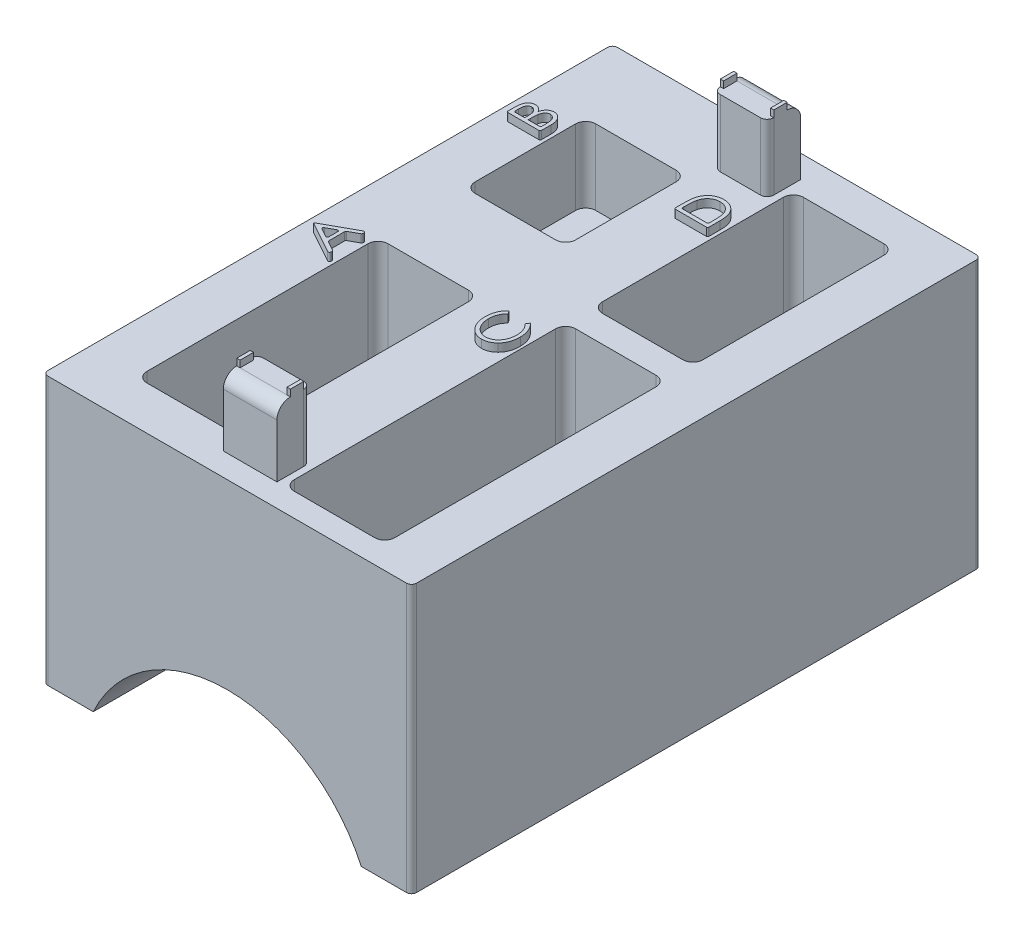
SolidWorks part; units mm, degrees
ref_plane "Front Plane" through (0, 0, 0) normal (0, 0, 1) x (1, 0, 0)
ref_plane "Top Plane" through (0, 0, 0) normal (0, 1, 0) x (1, 0, 0)
ref_plane "Right Plane" through (0, 0, 0) normal (1, 0, 0) x (0, 0, -1)
sketch "Sketch1" plane through (0, 0, 0) normal (0, 0, 1) x (1, 0, 0)
  line L0 (0, 0) -> (0, 52.7153) construction
  line L1 (-20, 0) -> (-20, 12.8504) construction
  line L2 (-20, 12.8504) -> (0, 12.8504) construction
  line L3 (-30.875, 0) -> (0, 0) construction
  line L4 (-20, 0) -> (-27.5, 0)
  line L5 (-27.5, 0) -> (-27.5, 40)
  line L6 (-27.5, 40) -> (27.5, 40)
  line L7 (20, 0) -> (27.5, 0)
  line L8 (27.5, 0) -> (27.5, 40)
  line L9 (0, 0) -> (0, -23.0796) construction
  arc A2 (20, 0) -> (-20, 0) centre (0, -9.1384) ccw
  point P15 (0, 40)
  dimension "D2" = 27.5
  dimension "D1" = 20
  dimension "D3" = 40
  dimension "D4" = 12.8504
  dimension "D6" = 12.8504
extrude "Boss-Extrude1" add sketch "Sketch1" along normal mid plane 85
sketch "Sketch2" plane through (0, 40, 0) normal (0, 1, 0) x (1, 0, 0)
  line L0 (0, 0) -> (0, 38.8612) construction
  line L1 (-33.2165, 0) -> (27.5, 0) construction
  line L2 (27.5, -42.5) -> (27.5, 42.5) construction
  line L3 (-12.5, -18) -> (12.5, -18) construction
  line L6 (-12.5, 22) -> (12.5, 22) construction
  line L10 (-20, -36) -> (-5, -36)
  line L11 (-20, -36) -> (-20, 0)
  line L12 (-20, 0) -> (-5, 0)
  line L13 (-5, -36) -> (-5, 0)
  line L14 (-20, -36) -> (-5, 0) construction
  line L15 (-20, 0) -> (-5, -36) construction
  line L16 (-5, 13) -> (-20, 13)
  line L17 (-5, 13) -> (-5, 31)
  line L18 (-5, 31) -> (-20, 31)
  line L19 (-20, 13) -> (-20, 31)
  line L20 (-5, 13) -> (-20, 31) construction
  line L21 (-5, 31) -> (-20, 13) construction
  line L22 (5, -39) -> (20, -39)
  line L23 (5, -39) -> (5, 3)
  line L24 (5, 3) -> (20, 3)
  line L25 (20, -39) -> (20, 3)
  line L26 (5, -39) -> (20, 3) construction
  line L27 (5, 3) -> (20, -39) construction
  line L28 (5, 7) -> (20, 7)
  line L29 (5, 7) -> (5, 37)
  line L30 (5, 37) -> (20, 37)
  line L31 (20, 7) -> (20, 37)
  line L32 (5, 7) -> (20, 37) construction
  line L33 (5, 37) -> (20, 7) construction
  point P11 (-12.5, -18)
  dimension "D1" = 25
  dimension "D2" = 18
  dimension "D3" = 15
  dimension "D4" = 36
  dimension "D5" = 15
  dimension "D6" = 18
  dimension "D7" = 42
  dimension "D8" = 15
  dimension "D9" = 30
  dimension "D10" = 15
  dimension "D11" = 22
extrude "Cut-Extrude1" cut sketch "Sketch2" against normal blind 20.4 contours L11 L12 L13 L10
extrude "Cut-Extrude2" cut sketch "Sketch2<4>" against normal blind 11.2 contours L19 L18 L17 L16
sketch "Sketch2<4>" plane through (0, 40, 0) normal (0, 1, 0) x (1, 0, 0) same geometry as "Sketch2"
extrude "Cut-Extrude3" cut sketch "Sketch2<5>" against normal blind 24.222 contours L23 L24 L25 L22
sketch "Sketch2<5>" plane through (0, 40, 0) normal (0, 1, 0) x (1, 0, 0) same geometry as "Sketch2"
extrude "Cut-Extrude4" cut sketch "Sketch2<6>" against normal blind 19.6 contours L29 L30 L31 L28
sketch "Sketch2<6>" plane through (0, 40, 0) normal (0, 1, 0) x (1, 0, 0) same geometry as "Sketch2"
fillet "Fillet1" radius 1.5 16 edges at (20, 27.889, 39) (20, 27.889, -3) (5, 27.889, 39) (5, 27.889, -3) (20, 30.2, -7) (20, 30.2, -37) (5, 30.2, -7) (5, 30.2, -37) (-5, 34.4, -31) (-20, 34.4, -31) (-5, 34.4, -13) (-20, 34.4, -13) (-5, 29.8, 36) (-20, 29.8, 36) (-5, 29.8, 0) (-20, 29.8, 0)
fillet "Fillet2" radius 0.75 4 edges at (-27.5, 20, -42.5) (27.5, 20, -42.5) (-27.5, 20, 42.5) (27.5, 20, 42.5)
sketch "Sketch5" plane through (0, 40, 0) normal (0, 1, 0) x (1, 0, 0)
  line L0 (-20.5, -7) -> (-20.5, 0) construction
  line L3 (-20.5, 24) -> (-20.5, 31.8267) construction
  line L6 (-20, -34.5) -> (-20, -1.5) construction
  line L7 (-18.5, 0) -> (-6.5, 0) construction
  line L9 (-6.5, 31) -> (-18.5, 31) construction
  line L10 (4.5, -7) -> (4.5, 3.2921) construction
  line L11 (4.5, 24) -> (4.5, 37.0546) construction
  line L13 (5, -37.5) -> (5, 1.5) construction
  line L16 (-20.5, -7) -> (6.6537, -7) construction
  line L17 (-20.5, 24) -> (4.5, 24) construction
  text T0 "A" font "Century Gothic" height 5
  text T1 "B" font "Century Gothic" height 5
  text T2 "C" font "Century Gothic" height 5
  text T3 "D" font "Century Gothic" height 5
  dimension "D1" = 0.5
  dimension "D2" = 7
  dimension "D3" = 7
  dimension "D4" = 0.5
extrude "Boss-Extrude2" add sketch "Sketch5" along normal blind 1.2
fillet "Fillet4" radius 0.2 18 edges at (-20.5, 40.6, 1.8668) (-20.5, 40.6, 6.2358) (0.0128, 40.6, -25.2821) (3.9872, 40.6, -25.2821) (4.5, 40.6, -24.7051) (-0.5, 40.6, -24.7051) (-25.5, 40.6, -24.7051) (-24.9872, 40.6, -25.2821) (-23.3846, 40.6, -25.2821) (-21.0128, 40.6, -25.2821) (-20.5, 40.6, -24.7051) (-20.5, 40.6, 1.2308) (-20.5, 40.6, 6.8718) (-22.1026, 40.6, 2.7512) (-22.1026, 40.6, 5.3524) (-22.6154, 40.6, 3.0327) (-22.6154, 40.6, 5.0689) (-24.4613, 40.6, 4.0513)
sketch "Sketch6" plane through (0, 40, 0) normal (0, 1, 0) x (1, 0, 0)
  line L0 (0, -19.0699) -> (0, -42.5) construction
  line L1 (26.75, -42.5) -> (-26.75, -42.5) construction
  line L2 (0, 33.8095) -> (0, 42.5) construction
  line L3 (26.75, 42.5) -> (-26.75, 42.5) construction
  line L4 (0, 0) -> (-30.0229, 0) construction
  line L5 (2, -39.0857) -> (-3, -39.0857)
  line L6 (4, -38.0857) -> (4, -35.0857)
  line L7 (2, -34.0857) -> (-3, -34.0857)
  line L8 (-4, -38.0857) -> (-4, -35.0857)
  line L9 (4, -39.0857) -> (-4, -34.0857) construction
  line L10 (4, -34.0857) -> (-4, -39.0857) construction
  line L11 (2.5, 34.0857) -> (-2.5, 34.0857)
  line L12 (4, 38.0857) -> (4, 35.0857)
  line L13 (-4, 38.0857) -> (-4, 35.0857)
  line L14 (2.5, 39.0857) -> (-2.5, 39.0857)
  line L15 (-3, -39.0857) -> (-4, -39.0857)
  line L16 (-4, -39.0857) -> (-4, -38.0857)
  line L17 (-4, -35.0857) -> (-4, -34.0857)
  line L18 (-4, -34.0857) -> (-3, -34.0857)
  line L19 (2, -34.0857) -> (4, -34.0857)
  line L20 (4, -34.0857) -> (4, -35.0857)
  line L21 (4, -38.0857) -> (4, -39.0857)
  line L22 (4, -39.0857) -> (2, -39.0857)
  line L23 (-2.5, 34.0857) -> (-4, 34.0857)
  line L24 (-4, 34.0857) -> (-4, 35.0857)
  line L25 (-4, 38.0857) -> (-4, 39.0857)
  line L26 (-4, 39.0857) -> (-2.5, 39.0857)
  line L27 (2.5, 39.0857) -> (4, 39.0857)
  line L28 (4, 39.0857) -> (4, 38.0857)
  line L29 (4, 35.0857) -> (4, 34.0857)
  line L30 (4, 34.0857) -> (2.5, 34.0857)
  point P8 (0, -36.5857)
  point P34 (4, 34.0857)
  point P37 (4, 39.0857)
  point P40 (-4, 39.0857)
  point P43 (-4, 34.0857)
  dimension "D1" = 5
  dimension "D2" = 8
extrude "Boss-Extrude3" add sketch "Sketch6" along normal blind 10
fillet "Fillet5" radius 2 2 edges at (0, 50, 39.0857) (0, 50, -39.0857)
fillet "Fillet6" radius 1 4 edges at (-4, 45, -34.0857) (4, 45, -34.0857) (-4, 45, 34.0857) (4, 45, 34.0857)
sketch "Sketch7" plane through (0, 50, 0) normal (0, 1, 0) x (1, 0, 0)
  line L0 (-3.5, -35.0857) -> (-3.5, -37.0857)
  line L1 (3.5, -37.0857) -> (3.5, -35.0857)
  line L2 (-3.5, -37.0857) -> (-4, -37.0857)
  line L3 (-3.5, -35.0857) -> (-4, -35.0857)
  line L4 (3, -34.0857) -> (-3, -34.0857)
  line L5 (-4, -35.0857) -> (-4, -37.0857)
  line L6 (-4, -37.0857) -> (4, -37.0857)
  line L7 (4, -37.0857) -> (4, -35.0857)
  line L9 (-4, -35.0857) -> (-4, -37.0857)
  line L11 (4, -37.0857) -> (4, -35.0857)
  line L12 (3.5, -35.0857) -> (4, -35.0857)
  line L13 (4, -37.0857) -> (3.5, -37.0857)
  arc A2 (-3, -34.0857) -> (-4, -35.0857) centre (-3, -35.0857) ccw
  arc A3 (4, -35.0857) -> (3, -34.0857) centre (3, -35.0857) ccw
  dimension "D1" = 0
  dimension "D2" = 0.5
extrude "Boss-Extrude4" add sketch "Sketch7" along normal blind 1
mirror "Mirror1" about plane through (0, 0, 0) normal (0, 0, 1) of "Boss-Extrude4"
